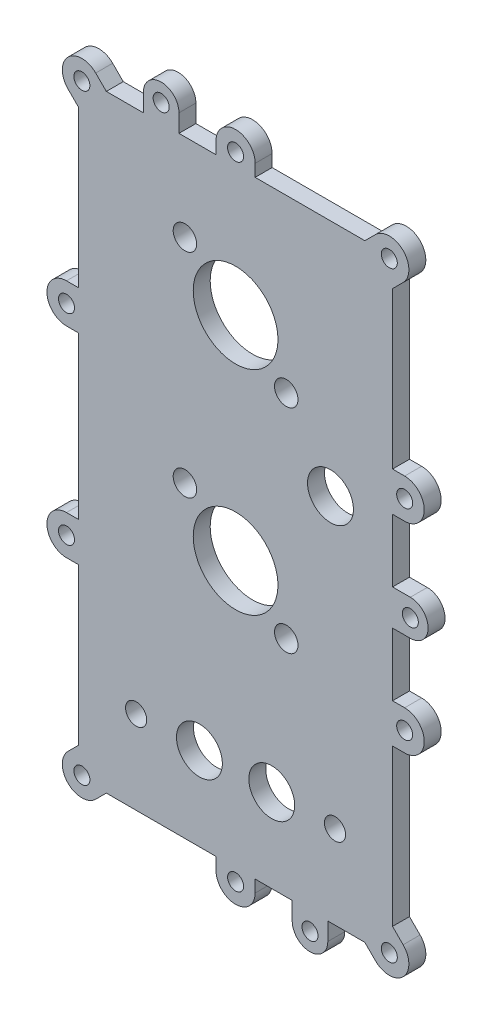
SolidWorks part; units mm, degrees
material "Acrylic (Medium-high impact)"
ref_plane "X-Y Datum" through (0, 0, 0) normal (0, 0, 1) x (1, 0, 0)
ref_plane "X-Z Datum" through (0, 0, 0) normal (0, 1, 0) x (1, 0, 0)
ref_plane "Y-Z Datum" through (0, 0, 0) normal (1, 0, 0) x (0, 0, -1)
sketch "Sketch1" plane through (0, 0, 0) normal (0, 0, 1) x (1, 0, 0)
  line L60 (50.35, 7.779) -> (19.5282, 7.779)
  line L61 (50.35, 11.1887) -> (50.35, 7.779)
  line L62 (61.35, 7.779) -> (61.35, 11.1887)
  line L63 (92.1718, 7.779) -> (61.35, 7.779)
  line L64 (95.1523, 10.7595) -> (92.1718, 7.779)
  line L65 (99.95, 0.0008) -> (102.9304, 2.9813)
  line L66 (99.95, -43.902) -> (99.95, 0.0008)
  line L67 (103.3597, -43.902) -> (99.95, -43.902)
  line L68 (99.95, -54.902) -> (103.3597, -54.902)
  line L69 (99.95, -100.29) -> (99.95, -54.902)
  line L70 (103.3597, -100.29) -> (99.95, -100.29)
  line L71 (99.95, -111.29) -> (103.3597, -111.29)
  line L72 (99.95, -155.1928) -> (99.95, -111.29)
  line L73 (102.9304, -158.1733) -> (99.95, -155.1928)
  line L74 (92.1718, -162.971) -> (95.1523, -165.9514)
  line L75 (61.35, -162.971) -> (92.1718, -162.971)
  line L76 (61.35, -166.3807) -> (61.35, -162.971)
  line L77 (50.35, -162.971) -> (50.35, -166.3807)
  line L78 (19.5282, -162.971) -> (50.35, -162.971)
  line L79 (16.5477, -165.9514) -> (19.5282, -162.971)
  line L80 (11.75, -155.1928) -> (8.7695, -158.1733)
  line L81 (11.75, -111.29) -> (11.75, -155.1928)
  line L82 (8.3403, -111.29) -> (11.75, -111.29)
  line L83 (11.75, -100.29) -> (8.3403, -100.29)
  line L84 (11.75, -54.902) -> (11.75, -100.29)
  line L85 (8.3403, -54.902) -> (11.75, -54.902)
  line L86 (11.75, -43.902) -> (8.3403, -43.902)
  line L87 (11.75, 0.0008) -> (11.75, -43.902)
  line L88 (8.7695, 2.9813) -> (11.75, 0.0008)
  line L89 (19.5282, 7.779) -> (16.5477, 10.7595)
  arc A20 (61.35, 11.1887) -> (50.35, 11.1887) centre (55.85, 11.1887) ccw
  arc A21 (102.9304, 2.9813) -> (95.1523, 10.7595) centre (99.0413, 6.8704) ccw
  arc A22 (103.3597, -54.902) -> (103.3597, -43.902) centre (103.3597, -49.402) ccw
  arc A23 (103.3597, -111.29) -> (103.3597, -100.29) centre (103.3597, -105.79) ccw
  arc A24 (95.1523, -165.9514) -> (102.9304, -158.1733) centre (99.0413, -162.0624) ccw
  arc A25 (50.35, -166.3807) -> (61.35, -166.3807) centre (55.85, -166.3807) ccw
  arc A26 (8.7695, -158.1733) -> (16.5477, -165.9514) centre (12.6586, -162.0624) ccw
  arc A27 (8.3403, -100.29) -> (8.3403, -111.29) centre (8.3403, -105.79) ccw
  arc A28 (8.3403, -43.902) -> (8.3403, -54.902) centre (8.3403, -49.402) ccw
  arc A29 (16.5477, 10.7595) -> (8.7695, 2.9813) centre (12.6586, 6.8704) ccw
extrude "Boss-Extrude1" add sketch "Sketch1" against normal blind 4.7625
hole_wizard "M4 Clearance Hole1" positions "Sketch2" profile "Sketch3" hole size "M4" standard "ANSI Metric" end condition through all
sketch "Sketch2" plane through (0, 0, -4.7625) normal (0, 0, -1) x (-1, 0, 0)
  point P0 (-12.6586, -162.0624)
  point P2 (-55.85, -166.3807)
  point P4 (-99.0413, -162.0624)
  point P6 (-103.3597, -105.79)
  point P8 (-103.3597, -49.402)
  point P10 (-99.0413, 6.8704)
  point P14 (-12.6586, 6.8704)
  point P16 (-8.3403, -49.402)
  point P18 (-8.3403, -105.79)
  point P22 (-55.85, 11.1887)
sketch "Sketch3" plane through (12.6586, -162.0624, -4.7625) normal (1, 0, 0) x (0, 1, 0)
  line L0 (0, 0) -> (0, 4.7625)
  line L1 (0, 4.7625) -> (2.25, 4.7625)
  line L2 (2.25, 4.7625) -> (2.25, 0)
  line L5 (2.25, 0) -> (0, 0)
  line L11 (0, -6.35) -> (0, 107.95) construction
  dimension "Thru Hole Dia." = 4.5
  dimension "Thru Hole Depth" = 4.7625
sketch "Sketch4" plane through (0, 0, -4.7625) normal (0, 0, -1) x (-1, 0, 0)
  line L8 (-93.95, -3.555) -> (-93.95, -119.546)
  line L9 (-93.95, -119.546) -> (-17.75, -119.546)
  line L10 (-17.75, -119.546) -> (-17.75, -3.555)
  line L11 (-23.084, 1.779) -> (-88.616, 1.779)
  line L16 (-95.5403, -3.555) -> (-95.5403, -151.637)
  line L17 (-88.616, -158.5613) -> (-23.084, -158.5613)
  line L18 (-16.1597, -151.637) -> (-16.1597, -3.555)
  line L19 (-23.084, 3.3693) -> (-88.616, 3.3693)
  line L24 (-93.95, -122.046) -> (-93.95, -151.637)
  line L25 (-17.75, -122.046) -> (-93.95, -122.046)
  line L26 (-17.75, -151.637) -> (-17.75, -122.046)
  line L27 (-88.616, -156.971) -> (-23.084, -156.971)
  circle A0 centre (-41.6161, -16.6659) radius 3.3
  circle A1 centre (-70.0839, -40.3003) radius 3.3
  circle A2 centre (-27.91, -139.5085) radius 2.9766
  circle A3 centre (-41.6161, -76.4667) radius 3.3
  circle A4 centre (-83.79, -139.5085) radius 2.9766
  circle A5 centre (-70.0839, -100.1011) radius 3.3
  arc A8 (-17.75, -3.555) -> (-23.084, 1.779) centre (-23.084, -3.555) ccw
  arc A9 (-88.616, 1.779) -> (-93.95, -3.555) centre (-88.616, -3.555) ccw
  circle A14 centre (-66.01, -139.5085) radius 6.445
  arc A16 (-95.5403, -151.637) -> (-88.616, -158.5613) centre (-88.616, -151.637) ccw
  arc A17 (-23.084, -158.5613) -> (-16.1597, -151.637) centre (-23.084, -151.637) ccw
  arc A18 (-16.1597, -3.555) -> (-23.084, 3.3693) centre (-23.084, -3.555) ccw
  arc A19 (-88.616, 3.3693) -> (-95.5403, -3.555) centre (-88.616, -3.555) ccw
  arc A22 (-23.084, -156.971) -> (-17.75, -151.637) centre (-23.084, -151.637) ccw
  arc A23 (-93.95, -151.637) -> (-88.616, -156.971) centre (-88.616, -151.637) ccw
  circle A32 centre (-82.52, -59.221) radius 6.445
  circle A34 centre (-45.69, -139.5085) radius 6.445
  circle A36 centre (-55.85, -88.2839) radius 11.9
  circle A38 centre (-55.85, -28.4831) radius 11.9
  dimension "D1" = 6.6
  dimension "D2" = 12.89
  dimension "D3" = 5.9531
  dimension "D4" = 23.8
  dimension "D5" = 12.89
  dimension "D6" = 55.88
extrude "Cut-Extrude1" cut sketch "Sketch4" against normal blind 4.7625 contours A38 | A32 | A36 | A2 | A34 | A14 | A4 | A0 | A1 | A3 | A5 region at (41.6161, -16.6659, -4.7625) region at (70.0839, -40.3003, -4.7625) region at (27.91, -139.5085, -4.7625) region at (41.6161, -76.4667, -4.7625) region at (83.79, -139.5085, -4.7625) region at (70.0839, -100.1011, -4.7625) region at (66.01, -139.5085, -4.7625) region at (82.52, -59.221, -4.7625) region at (45.69, -139.5085, -4.7625) region at (55.85, -88.2839, -4.7625) region at (55.85, -28.4831, -4.7625)
sketch "Sketch5" plane through (0, 0, -6.35) normal (0, 0, -1) x (-1, 0, 0)
  line L0 (-99.95, -77.596) -> (-104.95, -77.596) construction
  line L1 (-99.95, -100.29) -> (-99.95, -54.902) construction
  line L2 (-34.9391, 7.779) -> (-34.9391, 12.779) construction
  line L3 (-50.35, 7.779) -> (-19.5282, 7.779) construction
  line L4 (-76.7609, -162.971) -> (-76.7609, -167.971) construction
  line L6 (-61.35, -162.971) -> (-92.1718, -162.971) construction
  line L7 (-104.95, -72.596) -> (-99.95, -72.596)
  line L8 (-104.95, -82.596) -> (-99.95, -82.596)
  line L9 (-81.7609, -167.971) -> (-81.7609, -162.971)
  line L10 (-71.7609, -167.971) -> (-71.7609, -162.971)
  line L11 (-29.9391, 12.779) -> (-29.9391, 7.779)
  line L12 (-39.9391, 12.779) -> (-39.9391, 7.779)
  line L13 (-81.7609, -162.971) -> (-71.7609, -162.971)
  line L14 (-99.95, -82.596) -> (-99.95, -72.596)
  line L15 (-39.9391, 7.779) -> (-29.9391, 7.779)
  circle A1 centre (-103.3597, -105.79) radius 2.25
  circle A2 centre (-104.95, -77.596) radius 2.25 construction
  circle A3 centre (-34.9391, 12.779) radius 2.25 construction
  circle A4 centre (-76.7609, -167.971) radius 2.25 construction
  circle A5 centre (-104.95, -77.596) radius 4 construction
  circle A6 centre (-104.95, -77.596) radius 5
  circle A7 centre (-76.7609, -167.971) radius 5
  circle A8 centre (-34.9391, 12.779) radius 5
  dimension "D1" = 4.5
  dimension "D2" = 4.5
  dimension "D4" = 8
  dimension "D5" = 10
  dimension "D3" = 5
sketch "Sketch6" plane through (0, 0, 0) normal (0, 0, 1) x (1, 0, 0)
  line L0 (39.9391, 12.779) -> (39.9391, 7.779) construction
  line L1 (39.9391, 7.779) -> (29.9391, 7.779) construction
  line L2 (29.9391, 12.779) -> (29.9391, 7.779) construction
  line L3 (81.7609, -167.971) -> (81.7609, -162.971) construction
  line L4 (81.7609, -162.971) -> (71.7609, -162.971) construction
  line L5 (71.7609, -167.971) -> (71.7609, -162.971) construction
  line L6 (104.95, -72.596) -> (99.95, -72.596) construction
  line L7 (99.95, -82.596) -> (99.95, -72.596) construction
  line L8 (104.95, -82.596) -> (99.95, -82.596) construction
  line L9 (39.9391, 12.779) -> (39.9391, 7.779)
  line L10 (39.9391, 7.779) -> (29.9391, 7.779)
  line L11 (29.9391, 12.779) -> (29.9391, 7.779)
  line L12 (81.7609, -167.971) -> (81.7609, -162.971)
  line L13 (81.7609, -162.971) -> (71.7609, -162.971)
  line L14 (71.7609, -167.971) -> (71.7609, -162.971)
  line L15 (104.95, -72.596) -> (99.95, -72.596)
  line L16 (99.95, -82.596) -> (99.95, -72.596)
  line L17 (104.95, -82.596) -> (99.95, -82.596)
  circle A1 centre (103.3597, -105.79) radius 2.25
  circle A2 centre (103.3597, -105.79) radius 2.25
  circle A3 centre (34.9391, 12.779) radius 5
  circle A4 centre (34.9391, 12.779) radius 5
  circle A5 centre (76.7609, -167.971) radius 5
  circle A6 centre (76.7609, -167.971) radius 5
  circle A7 centre (104.95, -77.596) radius 5
  circle A8 centre (104.95, -77.596) radius 5
  dimension "D1" = 0
  dimension "D2" = 0
  dimension "D3" = 0
  dimension "D4" = 0
extrude "Boss-Extrude3" add sketch "Sketch6" against normal blind 4.7625 contours A6 L12 L13 L14 | A8 L15 L16 L17 | A8 | A4 L11 L10 L9 | A4 | A8 L16 L17 | A4 L10 L9 | A6 L13 L14 | A6 region at (34.9391, 12.779, 0) region at (38.8222, 8.8959, 0) region at (31.0559, 8.8959, 0) region at (80.644, -164.0878, 0) region at (72.8777, -164.0878, 0) region at (101.0668, -73.7128, 0) region at (104.95, -77.596, 0) region at (101.0668, -81.4791, 0)
hole_wizard "M4 Clearance Hole2" positions "Sketch8" profile "Sketch9" hole size "M4" standard "ANSI Metric" end condition through all
sketch "Sketch8" plane through (0, 0, 0) normal (0, 0, 1) x (1, 0, 0)
  point P11 (34.9391, 12.779)
  point P13 (104.95, -77.596)
  point P15 (76.7609, -167.971)
sketch "Sketch9" plane through (34.9391, 12.779, 0) normal (1, 0, 0) x (0, -1, 0)
  line L0 (0, 0) -> (0, 4.7625)
  line L1 (0, 4.7625) -> (2.25, 4.7625)
  line L2 (2.25, 4.7625) -> (2.25, 0)
  line L5 (2.25, 0) -> (0, 0)
  line L11 (0, -6.35) -> (0, 107.95) construction
  dimension "Thru Hole Dia." = 4.5
  dimension "Thru Hole Depth" = 4.7625
